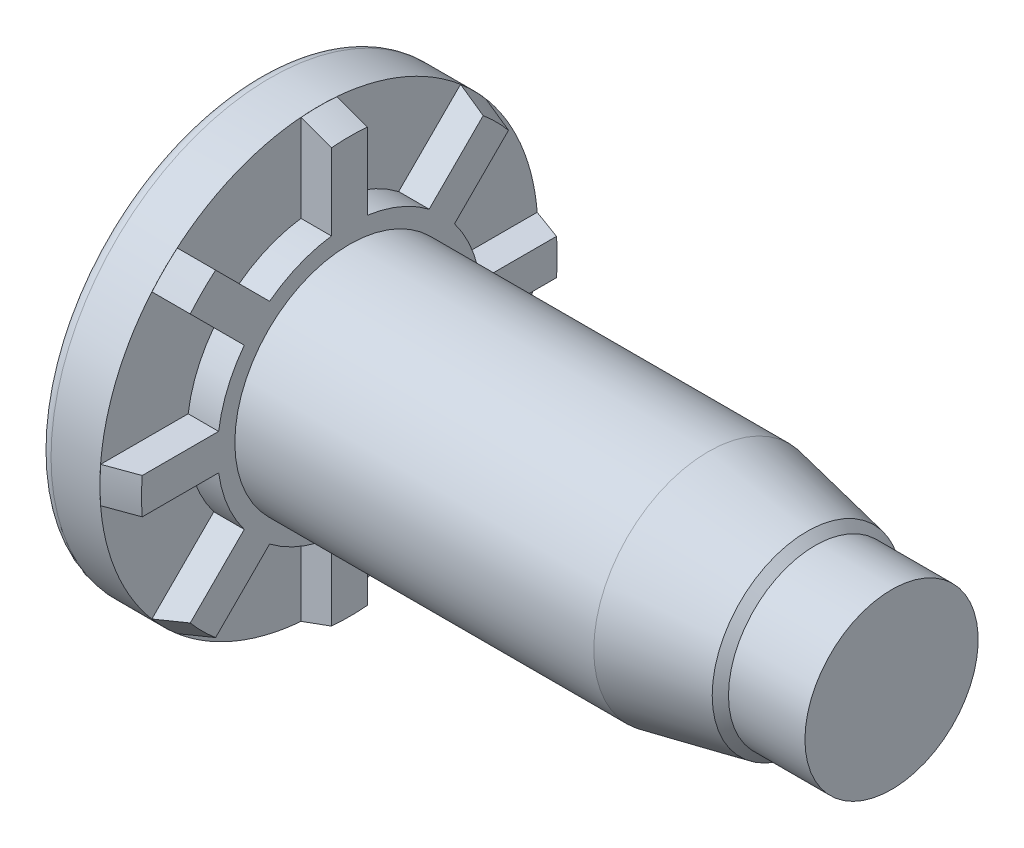
SolidWorks part; units mm, degrees
revolve "BaseBody" add sketch "BodySke" angle 360 about L6 other way angle 7.5
sketch "BodySke" plane through (0, 0, 0) normal (0, 0, 1) x (1, 0, 0)
  line L0 (-2.13, 7.224) -> (-2.13, 0)
  line L1 (1.065, 7.2608) -> (1.065, 4)
  line L2 (0.0025, 7.6475) -> (1.065, 7.2608)
  line L3 (1.065, 4) -> (13.6, 4)
  line L4 (13.6, 4) -> (17.0455, 3.3095)
  line L5 (20, 0) -> (-2.13, 0)
  line L6 (0, 0) -> (50.554, 0) construction
  line L7 (17.33, 3.025) -> (20, 3.025)
  line L8 (17.33, 3.025) -> (17.0455, 3.3095)
  line L9 (-1.704, 7.65) -> (0, 7.65)
  line L10 (0.0025, 7.6475) -> (0, 7.6475)
  line L11 (1.25, 19.05) -> (1.25, -3.175) construction
  line L12 (0, 7.6475) -> (0, 7.65)
  line L13 (20, 3.025) -> (20, 0)
  arc A0 (-2.13, 7.224) -> (-1.704, 7.65) centre (-1.704, 7.224) cw
  dimension "Fillet_rad" = 0.426
  dimension "T_dim" = 2.13
  dimension "H_dia" = 15.3
  dimension "D2" = 0.0025
  dimension "D3" = 0.0025
  dimension "Advance" = 1.25
  dimension "D1" = 20
  dimension "Length" = 20
  dimension "D4" = 45
  dimension "Diameter" = 8
  dimension "Minor_dia" = 6.619
cosmetic thread "ThreadCosmetic" [suppressed] parameters "Thread_length"=13.7455, "Thread_minor"=6.619
ref_plane "Plane1" through (0, 0, 0) normal (0, 0, 1) x (1, 0, 0)
ref_plane "Plane2" through (0, 0, 0) normal (0, 1, 0) x (1, 0, 0)
ref_plane "Plane3" through (0, 0, 0) normal (1, 0, 0) x (0, 0, -1)
sketch "ThdSchSke" plane through (0, 0, 0) normal (0, 0, 1) x (1, 0, 0)
  line L0 (3.3, -3.3095) -> (2.8165, -4)
  line L1 (3.3, -3.3095) -> (3.7835, -4)
  line L2 (3.7835, -4) -> (3.7835, -5)
  line L3 (-3.175, 0) -> (5.1513, 0) construction
  line L4 (0, -7.65) -> (0, 7.65) construction
  line L5 (3.7835, -5) -> (2.8165, -5)
  line L6 (2.8165, -5) -> (2.8165, -4)
  line L7 (21.3518, 6.5809) -> (21.3518, 1.1961) construction
  dimension "Diameter" = 8
  dimension "Thread_minor" = 6.619
  dimension "Start" = 3.3
revolve "ThreadSchematic" [suppressed] cut sketch "ThdSchSke" angle 360 about L3
pattern_linear "ThdSchPat" [suppressed]
sketch "RibCutSke" plane through (1.065, 1.7944, -0.091) normal (1, 0, 0) x (0, 0, -1)
  line L0 (0.5348, 2.7713) -> (0.5348, 5.83)
  line L1 (2.695, 1.8765) -> (4.8578, 4.0393)
  line L2 (0.5348, 2.1564) -> (0.5348, 2.4006) construction
  line L3 (-0.091, -1.7944) -> (-0.091, 5.0239) construction
  line L4 (-0.091, -1.7944) -> (0.5348, 2.1564) construction
  line L5 (-0.091, -1.7944) -> (2.2602, 1.4417) construction
  line L6 (2.2602, 1.4417) -> (2.4379, 1.6194) construction
  arc A1 (2.695, 1.8765) -> (0.5348, 2.7713) centre (-0.091, -1.7944) ccw
  arc A2 (4.8578, 4.0393) -> (0.5348, 5.83) centre (-0.091, -1.7944) ccw
  circle A3 centre (-0.091, -1.7944) radius 7.2608 construction
  circle A4 centre (-0.091, -1.7944) radius 4 construction
  dimension "Rib_root_half_angle" = 9
  dimension "Rib_root_gap_angle" = 27
  dimension "Angle" = 45
extrude "RibCut" cut sketch "RibCutSke" against normal blind 1.065
pattern_circular "RibCutsPat" count 8 every 45 about axis through (0, 0, 0) along (1, 0, 0) of "RibCut"
equation "' \"Length@BodySke\" = 20"
equation "' \"H_dia@BodySke\" = 15.3"
equation "' \"Start@ThdSchSke\" = 3.3"
equation "' \"T_dim@BodySke\" = 2.13"
equation "' \"Dog_dia@BodySke\" = 6.05"
equation "' \"Dog_len@BodySke\" = 2.67"
equation "' \"Thread_trans@BodySke\" = 3.73"
equation "' \"Diameter@BodySke\" = 8"
equation "' \"Minor_dia@BodySke\" =  6.619"
equation "' \"Minor_dia@BodySke\" = 6.619"
equation "' \"Advance@BodySke\" = 1.25"
equation "\"Fillet_rad@BodySke\" =  \"T_dim@BodySke\" * 0.2"
equation "\"Clinch_ht@BodySke\" = \"T_dim@BodySke\" * 0.5"
equation "\"Num_ribs@RibCutsPat\" = 8"
equation "\"Angle@RibCutSke\" =\"Angle@RibCutsPat\""
equation "\"Rib_root_half_angle@RibCutSke\" = \"Angle@RibCutSke\" / 5"
equation "\"Rib_root_gap_angle@RibCutSke\" = \"Angle@RibCutSke\" - (2 * \"Rib_root_half_angle@RibCutSke\" )"
equation "\"Rib_root_dia@RibCutSke\" = \"Diameter@BodySke\""
equation "\"Inner_dia@RibCutSke\" = \"Diameter@BodySke\" + ( \"H_dia@BodySke\" - \"Diameter@BodySke\" ) / 6"
equation "\"Outer_dia@RibCutSke\" = \"H_dia@BodySke\""
equation "\"Depth@RibCut\" = \"Clinch_ht@BodySke\""
equation "\"Thread_length@ThreadCosmetic\" = \"Length@BodySke\" - \"Start@ThdSchSke\"  - \"Dog_len@BodySke\"  - ( \"Minor_dia@BodySke\" - \"Dog_dia@BodySke\" ) / 2"
equation "\"Thread_minor@ThreadCosmetic\" = \"Minor_dia@BodySke\""
equation "\"Thread_minor@ThdSchSke\" = \"Minor_dia@BodySke\""
equation "\"Diameter@ThdSchSke\" = \"Diameter@BodySke\""
equation "\"Overcut@ThdSchSke\" = \"Diameter@BodySke\" * 1.25"
equation "\"Num_threads@ThdSchPat\" = int( \"Thread_length@ThreadCosmetic\" / \"Advance@BodySke\" + 0.999 )  + 1"
equation "\"Advance@ThdSchPat\" = \"Thread_length@ThreadCosmetic\" /  (\"Num_threads@ThdSchPat\" - 1) 'relax it"
equation "\"Num_threads@ThdSchPat\" = \"Num_threads@ThdSchPat\" - sgn( \"Num_threads@ThdSchPat\" - 1) '---chamfered tips only---"
